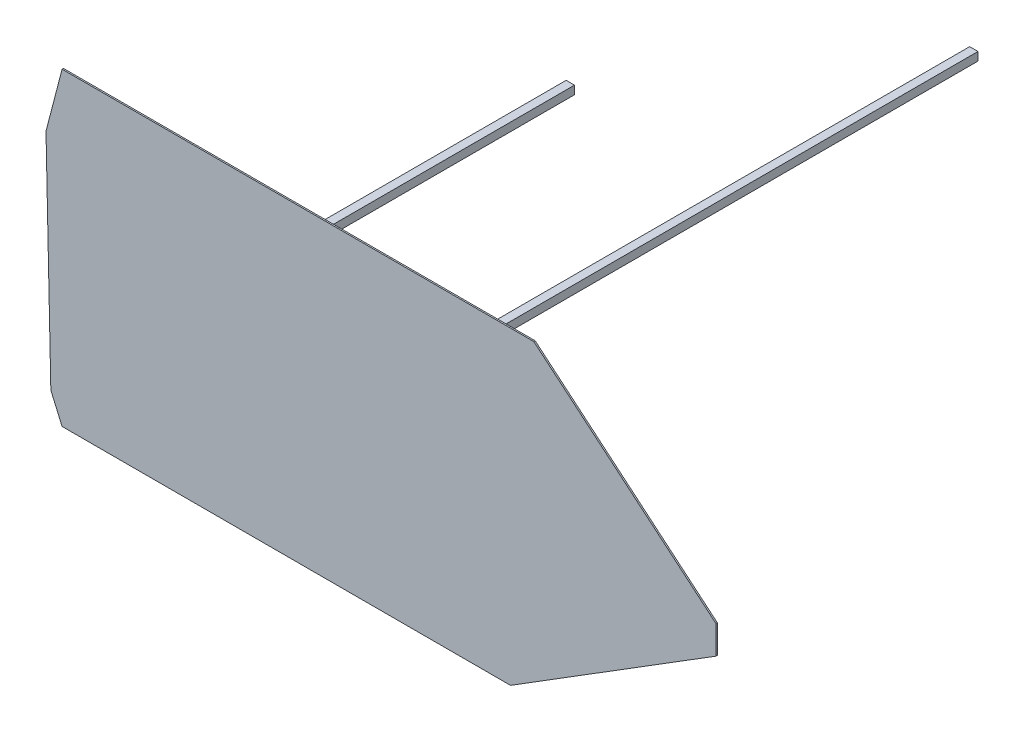
SolidWorks part; units mm, degrees
ref_plane "Front" through (0, 0, 0) normal (0, 0, 1) x (1, 0, 0)
ref_plane "Top" through (0, 0, 0) normal (0, 1, 0) x (1, 0, 0)
ref_plane "Right" through (0, 0, 0) normal (1, 0, 0) x (0, 0, -1)
sketch "Esquisse1" plane through (0, 0, 0) normal (0, 0, 1) x (1, 0, 0)
  line L1 (0, 0) -> (50, 0)
  line L2 (0, 0) -> (0, 50)
  line L3 (0, 50) -> (50, 50)
  line L4 (50, 0) -> (50, 50)
  dimension "D1" = 50
  dimension "D2" = 50
extrude "Boss.-Extru.1" add sketch "Esquisse1" along normal blind 5
sketch "Esquisse2" plane through (0, 0, 5) normal (0, 0, 1) x (1, 0, 0)
  line L0 (-5.6535, 9.3332) -> (57.2852, 53.4636)
  line L1 (57.2852, 53.4636) -> (231.6916, 53.4636)
  line L2 (231.6916, 53.4636) -> (285.9358, -3.0527)
  line L3 (285.9358, -3.0527) -> (284, -82.5096)
  line L4 (284, -82.5096) -> (207.7062, -129.7611)
  line L5 (207.7062, -129.7611) -> (50.4315, -129.7611)
  line L6 (50.4315, -129.7611) -> (-5.6535, -85.3866)
  line L7 (-5.6535, -85.3866) -> (-5.6535, 9.3332)
  line L8 (261, -129.7611) -> (23, -129.7611) construction
  line L9 (284, 24.7389) -> (284, -104.2611) construction
extrude "Boss.-Extru.2" add sketch "Esquisse2" against normal up to vertex (5 mm away) up to point (0, 50, 0)
sketch "Esquisse3" plane through (0, 0, 0) normal (0, 0, -1) x (-1, 0, 0)
  line L0 (0, -121.7217) -> (6, -121.7217)
  line L1 (6, -121.7217) -> (6, -115.7217)
  line L2 (6, -115.7217) -> (0, -115.7217)
  line L4 (0, -115.7217) -> (0, -121.7217)
  line L6 (-284, 44.2389) -> (-290, 44.2389)
  line L7 (-284, 44.2389) -> (-284, 50.2389)
  line L8 (-284, 50.2389) -> (-290, 50.2389)
  line L9 (-290, 44.2389) -> (-290, 50.2389)
  dimension "D1" = 6
  dimension "D2" = 6
  dimension "D3" = 6
  dimension "D4" = 6
extrude "Boss.-Extru.3" add sketch "Esquisse3" along normal blind 350
sketch "Esquisse4" plane through (0, 0, 5) normal (0, 0, 1) x (1, 0, 0)
  line L0 (-12.2793, 66.0481) -> (326.7277, 66.0481)
  line L1 (326.7277, 66.0481) -> (457.7032, -44.0432)
  line L2 (457.7032, -44.0432) -> (457.7032, -64.2948)
  line L3 (457.7032, -64.2948) -> (309.9939, -156.3257)
  line L4 (309.9939, -156.3257) -> (-12.2793, -156.3257)
  line L5 (-12.2793, -156.3257) -> (-20.3705, -137.7747)
  line L6 (-20.3705, -137.7747) -> (-23.8479, 21.7019)
  line L7 (-23.8479, 21.7019) -> (-12.2793, 66.0481)
  point P2 (425.3985, -68.9186)
  point P9 (316.7824, -151.1841)
  point P10 (-12.2793, -156.3257)
  point P11 (-24.4906, -5.2915)
  point P12 (-12.2793, 66.0481)
  point P13 (-23.8479, 21.7019)
  point P14 (456.0216, -65.3425)
  point P15 (457.7032, -44.0432)
extrude "Boss.-Extru.4" add sketch "Esquisse4" along normal blind 1
